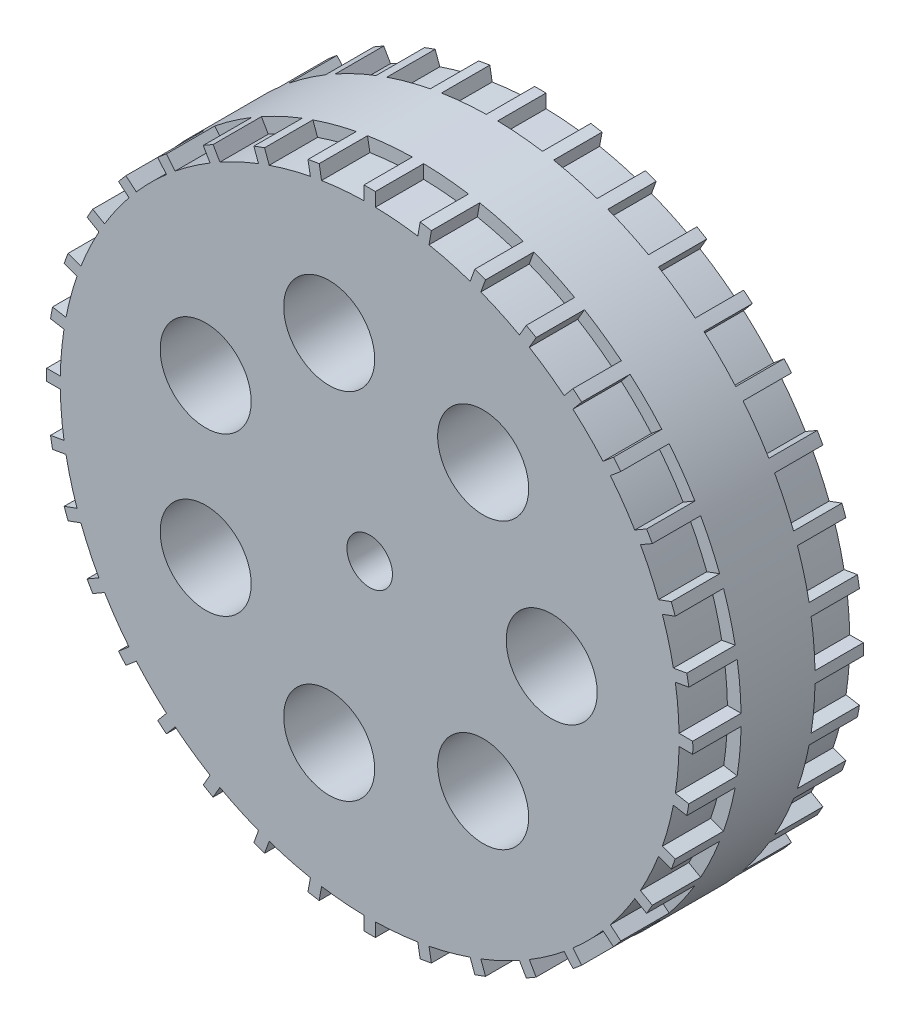
SolidWorks part; units mm, degrees
material "ABS"
ref_plane "前视基准面" through (0, 0, 0) normal (0, 0, 1) x (1, 0, 0)
ref_plane "上视基准面" through (0, 0, 0) normal (0, 1, 0) x (1, 0, 0)
ref_plane "右视基准面" through (0, 0, 0) normal (1, 0, 0) x (0, 0, -1)
sketch "草图1" plane through (0, 0, 0) normal (0, 0, 1) x (1, 0, 0)
  circle A0 centre (0, 0) radius 27.2
  dimension "D1" = 54.4
extrude "凸台-拉伸1" add sketch "草图1" along normal blind 15
sketch "草图2" plane through (0, 0, 0) normal (0, 0, -1) x (-1, 0, 0)
  line L1 (7.0437, 0) -> (3.5218, 6.1)
  line L2 (3.5218, 6.1) -> (-3.5218, 6.1)
  line L3 (-3.5218, 6.1) -> (-7.0437, 0)
  line L4 (-7.0437, 0) -> (-3.5218, -6.1)
  line L5 (-3.5218, -6.1) -> (3.5218, -6.1)
  line L6 (3.5218, -6.1) -> (7.0437, 0)
  circle A0 centre (0, 0) radius 6.1 construction
  dimension "D1" = 12.2
extrude "切除-拉伸1" cut sketch "草图2" against normal blind 10
sketch "草图3" plane through (0, 0, 10) normal (0, 0, -1) x (-1, 0, 0)
  circle A0 centre (0, 0) radius 2
  dimension "D1" = 4
extrude "切除-拉伸2" cut sketch "草图3" against normal blind 11
sketch "草图6" plane through (0, 0, 15) normal (0, 0, 1) x (1, 0, 0)
  circle A0 centre (16, 0) radius 4
  circle A1 centre (9.9758, -12.5093) radius 4
  circle A2 centre (-3.5603, -15.5988) radius 4
  circle A3 centre (-14.4155, -6.9421) radius 4
  circle A4 centre (-14.4155, 6.9421) radius 4
  circle A5 centre (-3.5603, 15.5988) radius 4
  circle A6 centre (9.9758, 12.5093) radius 4
  circle A7 centre (0, 0) radius 2 construction
  point P16 (0, 0)
  point P19 (0, 0)
  dimension "D1" = 8
  dimension "D2" = 7
  dimension "D3" = 16
extrude "切除-拉伸5" cut sketch "草图6" against normal blind 30
sketch "草图7" plane through (0, 0, 15) normal (0, 0, 1) x (1, 0, 0)
  line L0 (0, 27.2) -> (0, 28.4) construction
  line L1 (-0.5, 28.3956) -> (-0.5, 27.1954)
  line L2 (0.5, 28.3956) -> (0.5, 27.1954)
  line L3 (4.4384, 28.051) -> (4.23, 26.8691)
  line L4 (5.4232, 27.8774) -> (5.2148, 26.6954)
  line L5 (9.242, 26.8541) -> (8.8315, 25.7263)
  line L6 (10.1817, 26.5121) -> (9.7712, 25.3843)
  line L7 (13.7648, 24.8413) -> (13.1647, 23.8019)
  line L8 (14.6308, 24.3413) -> (14.0307, 23.3019)
  line L9 (17.8693, 22.0737) -> (17.0978, 21.1543)
  line L10 (18.6354, 21.4309) -> (17.8639, 20.5115)
  line L11 (21.4309, 18.6354) -> (20.5115, 17.8639)
  line L12 (22.0737, 17.8693) -> (21.1543, 17.0978)
  line L13 (24.3413, 14.6308) -> (23.3019, 14.0307)
  line L14 (24.8413, 13.7648) -> (23.8019, 13.1647)
  line L15 (26.5121, 10.1817) -> (25.3843, 9.7712)
  line L16 (26.8541, 9.242) -> (25.7263, 8.8315)
  line L17 (27.8774, 5.4232) -> (26.6954, 5.2148)
  line L18 (28.051, 4.4384) -> (26.8691, 4.23)
  line L19 (28.3956, 0.5) -> (27.1954, 0.5)
  line L20 (28.3956, -0.5) -> (27.1954, -0.5)
  line L21 (28.051, -4.4384) -> (26.8691, -4.23)
  line L22 (27.8774, -5.4232) -> (26.6954, -5.2148)
  line L23 (26.8541, -9.242) -> (25.7263, -8.8315)
  line L24 (26.5121, -10.1817) -> (25.3843, -9.7712)
  line L25 (24.8413, -13.7648) -> (23.8019, -13.1647)
  line L26 (24.3413, -14.6308) -> (23.3019, -14.0307)
  line L27 (22.0737, -17.8693) -> (21.1543, -17.0978)
  line L28 (21.4309, -18.6354) -> (20.5115, -17.8639)
  line L29 (18.6354, -21.4309) -> (17.8639, -20.5115)
  line L30 (17.8693, -22.0737) -> (17.0978, -21.1543)
  line L31 (14.6308, -24.3413) -> (14.0307, -23.3019)
  line L32 (13.7648, -24.8413) -> (13.1647, -23.8019)
  line L33 (10.1817, -26.5121) -> (9.7712, -25.3843)
  line L34 (9.242, -26.8541) -> (8.8315, -25.7263)
  line L35 (5.4232, -27.8774) -> (5.2148, -26.6954)
  line L36 (4.4384, -28.051) -> (4.23, -26.8691)
  line L37 (0.5, -28.3956) -> (0.5, -27.1954)
  line L38 (-0.5, -28.3956) -> (-0.5, -27.1954)
  line L39 (-4.4384, -28.051) -> (-4.23, -26.8691)
  line L40 (-5.4232, -27.8774) -> (-5.2148, -26.6954)
  line L41 (-9.242, -26.8541) -> (-8.8315, -25.7263)
  line L42 (-10.1817, -26.5121) -> (-9.7712, -25.3843)
  line L43 (-13.7648, -24.8413) -> (-13.1647, -23.8019)
  line L44 (-14.6308, -24.3413) -> (-14.0307, -23.3019)
  line L45 (-17.8693, -22.0737) -> (-17.0978, -21.1543)
  line L46 (-18.6354, -21.4309) -> (-17.8639, -20.5115)
  line L47 (-21.4309, -18.6354) -> (-20.5115, -17.8639)
  line L48 (-22.0737, -17.8693) -> (-21.1543, -17.0978)
  line L49 (-24.3413, -14.6308) -> (-23.3019, -14.0307)
  line L50 (-24.8413, -13.7648) -> (-23.8019, -13.1647)
  line L51 (-26.5121, -10.1817) -> (-25.3843, -9.7712)
  line L52 (-26.8541, -9.242) -> (-25.7263, -8.8315)
  line L53 (-27.8774, -5.4232) -> (-26.6954, -5.2148)
  line L54 (-28.051, -4.4384) -> (-26.8691, -4.23)
  line L55 (-28.3956, -0.5) -> (-27.1954, -0.5)
  line L56 (-28.3956, 0.5) -> (-27.1954, 0.5)
  line L57 (-28.051, 4.4384) -> (-26.8691, 4.23)
  line L58 (-27.8774, 5.4232) -> (-26.6954, 5.2148)
  line L59 (-26.8541, 9.242) -> (-25.7263, 8.8315)
  line L60 (-26.5121, 10.1817) -> (-25.3843, 9.7712)
  line L61 (-24.8413, 13.7648) -> (-23.8019, 13.1647)
  line L62 (-24.3413, 14.6308) -> (-23.3019, 14.0307)
  line L63 (-22.0737, 17.8693) -> (-21.1543, 17.0978)
  line L64 (-21.4309, 18.6354) -> (-20.5115, 17.8639)
  line L65 (-18.6354, 21.4309) -> (-17.8639, 20.5115)
  line L66 (-17.8693, 22.0737) -> (-17.0978, 21.1543)
  line L67 (-14.6308, 24.3413) -> (-14.0307, 23.3019)
  line L68 (-13.7648, 24.8413) -> (-13.1647, 23.8019)
  line L69 (-10.1817, 26.5121) -> (-9.7712, 25.3843)
  line L70 (-9.242, 26.8541) -> (-8.8315, 25.7263)
  line L71 (-5.4232, 27.8774) -> (-5.2148, 26.6954)
  line L72 (-4.4384, 28.051) -> (-4.23, 26.8691)
  arc A0 (0.5, 27.1954) -> (-0.5, 27.1954) centre (0, 0) ccw
  arc A1 (0.5, 28.3956) -> (-0.5, 28.3956) centre (0, 0) ccw
  arc A2 (5.4232, 27.8774) -> (4.4384, 28.051) centre (0, 0) ccw
  arc A3 (5.2148, 26.6954) -> (4.23, 26.8691) centre (0, 0) ccw
  arc A4 (10.1817, 26.5121) -> (9.242, 26.8541) centre (0, 0) ccw
  arc A5 (9.7712, 25.3843) -> (8.8315, 25.7263) centre (0, 0) ccw
  arc A6 (14.6308, 24.3413) -> (13.7648, 24.8413) centre (0, 0) ccw
  arc A7 (14.0307, 23.3019) -> (13.1647, 23.8019) centre (0, 0) ccw
  arc A8 (18.6354, 21.4309) -> (17.8693, 22.0737) centre (0, 0) ccw
  arc A9 (17.8639, 20.5115) -> (17.0978, 21.1543) centre (0, 0) ccw
  arc A10 (22.0737, 17.8693) -> (21.4309, 18.6354) centre (0, 0) ccw
  arc A11 (21.1543, 17.0978) -> (20.5115, 17.8639) centre (0, 0) ccw
  arc A12 (24.8413, 13.7648) -> (24.3413, 14.6308) centre (0, 0) ccw
  arc A13 (23.8019, 13.1647) -> (23.3019, 14.0307) centre (0, 0) ccw
  arc A14 (26.8541, 9.242) -> (26.5121, 10.1817) centre (0, 0) ccw
  arc A15 (25.7263, 8.8315) -> (25.3843, 9.7712) centre (0, 0) ccw
  arc A16 (28.051, 4.4384) -> (27.8774, 5.4232) centre (0, 0) ccw
  arc A17 (26.8691, 4.23) -> (26.6954, 5.2148) centre (0, 0) ccw
  arc A18 (28.3956, -0.5) -> (28.3956, 0.5) centre (0, 0) ccw
  arc A19 (27.1954, -0.5) -> (27.1954, 0.5) centre (0, 0) ccw
  arc A20 (27.8774, -5.4232) -> (28.051, -4.4384) centre (0, 0) ccw
  arc A21 (26.6954, -5.2148) -> (26.8691, -4.23) centre (0, 0) ccw
  arc A22 (26.5121, -10.1817) -> (26.8541, -9.242) centre (0, 0) ccw
  arc A23 (25.3843, -9.7712) -> (25.7263, -8.8315) centre (0, 0) ccw
  arc A24 (24.3413, -14.6308) -> (24.8413, -13.7648) centre (0, 0) ccw
  arc A25 (23.3019, -14.0307) -> (23.8019, -13.1647) centre (0, 0) ccw
  arc A26 (21.4309, -18.6354) -> (22.0737, -17.8693) centre (0, 0) ccw
  arc A27 (20.5115, -17.8639) -> (21.1543, -17.0978) centre (0, 0) ccw
  arc A28 (17.8693, -22.0737) -> (18.6354, -21.4309) centre (0, 0) ccw
  arc A29 (17.0978, -21.1543) -> (17.8639, -20.5115) centre (0, 0) ccw
  arc A30 (13.7648, -24.8413) -> (14.6308, -24.3413) centre (0, 0) ccw
  arc A31 (13.1647, -23.8019) -> (14.0307, -23.3019) centre (0, 0) ccw
  arc A32 (9.242, -26.8541) -> (10.1817, -26.5121) centre (0, 0) ccw
  arc A33 (8.8315, -25.7263) -> (9.7712, -25.3843) centre (0, 0) ccw
  arc A34 (4.4384, -28.051) -> (5.4232, -27.8774) centre (0, 0) ccw
  arc A35 (4.23, -26.8691) -> (5.2148, -26.6954) centre (0, 0) ccw
  arc A36 (-0.5, -28.3956) -> (0.5, -28.3956) centre (0, 0) ccw
  arc A37 (-0.5, -27.1954) -> (0.5, -27.1954) centre (0, 0) ccw
  arc A38 (-5.4232, -27.8774) -> (-4.4384, -28.051) centre (0, 0) ccw
  arc A39 (-5.2148, -26.6954) -> (-4.23, -26.8691) centre (0, 0) ccw
  arc A40 (-10.1817, -26.5121) -> (-9.242, -26.8541) centre (0, 0) ccw
  arc A41 (-9.7712, -25.3843) -> (-8.8315, -25.7263) centre (0, 0) ccw
  arc A42 (-14.6308, -24.3413) -> (-13.7648, -24.8413) centre (0, 0) ccw
  arc A43 (-14.0307, -23.3019) -> (-13.1647, -23.8019) centre (0, 0) ccw
  arc A44 (-18.6354, -21.4309) -> (-17.8693, -22.0737) centre (0, 0) ccw
  arc A45 (-17.8639, -20.5115) -> (-17.0978, -21.1543) centre (0, 0) ccw
  arc A46 (-22.0737, -17.8693) -> (-21.4309, -18.6354) centre (0, 0) ccw
  arc A47 (-21.1543, -17.0978) -> (-20.5115, -17.8639) centre (0, 0) ccw
  arc A48 (-24.8413, -13.7648) -> (-24.3413, -14.6308) centre (0, 0) ccw
  arc A49 (-23.8019, -13.1647) -> (-23.3019, -14.0307) centre (0, 0) ccw
  arc A50 (-26.8541, -9.242) -> (-26.5121, -10.1817) centre (0, 0) ccw
  arc A51 (-25.7263, -8.8315) -> (-25.3843, -9.7712) centre (0, 0) ccw
  arc A52 (-28.051, -4.4384) -> (-27.8774, -5.4232) centre (0, 0) ccw
  arc A53 (-26.8691, -4.23) -> (-26.6954, -5.2148) centre (0, 0) ccw
  arc A54 (-28.3956, 0.5) -> (-28.3956, -0.5) centre (0, 0) ccw
  arc A55 (-27.1954, 0.5) -> (-27.1954, -0.5) centre (0, 0) ccw
  arc A56 (-27.8774, 5.4232) -> (-28.051, 4.4384) centre (0, 0) ccw
  arc A57 (-26.6954, 5.2148) -> (-26.8691, 4.23) centre (0, 0) ccw
  arc A58 (-26.5121, 10.1817) -> (-26.8541, 9.242) centre (0, 0) ccw
  arc A59 (-25.3843, 9.7712) -> (-25.7263, 8.8315) centre (0, 0) ccw
  arc A60 (-24.3413, 14.6308) -> (-24.8413, 13.7648) centre (0, 0) ccw
  arc A61 (-23.3019, 14.0307) -> (-23.8019, 13.1647) centre (0, 0) ccw
  arc A62 (-21.4309, 18.6354) -> (-22.0737, 17.8693) centre (0, 0) ccw
  arc A63 (-20.5115, 17.8639) -> (-21.1543, 17.0978) centre (0, 0) ccw
  arc A64 (-17.8693, 22.0737) -> (-18.6354, 21.4309) centre (0, 0) ccw
  arc A65 (-17.0978, 21.1543) -> (-17.8639, 20.5115) centre (0, 0) ccw
  arc A66 (-13.7648, 24.8413) -> (-14.6308, 24.3413) centre (0, 0) ccw
  arc A67 (-13.1647, 23.8019) -> (-14.0307, 23.3019) centre (0, 0) ccw
  arc A68 (-9.242, 26.8541) -> (-10.1817, 26.5121) centre (0, 0) ccw
  arc A69 (-8.8315, 25.7263) -> (-9.7712, 25.3843) centre (0, 0) ccw
  arc A70 (-4.4384, 28.051) -> (-5.4232, 27.8774) centre (0, 0) ccw
  arc A71 (-4.23, 26.8691) -> (-5.2148, 26.6954) centre (0, 0) ccw
  point P150 (0, 0)
  dimension "D1" = 54.4
  dimension "D2" = 56.8
  dimension "D3" = 0.5
  dimension "D4" = 36
extrude "凸台-拉伸2" add sketch "草图7" against normal up to surface (15 mm away) up to face at (13.9758, -12.5093, 0)
ref_plane "基准面1" through (0, 0, 7.5) normal (0, 0, 1) x (1, 0, 0)
sketch "草图10" plane through (0, 0, 7.5) normal (0, 0, 1) x (1, 0, 0)
  circle A0 centre (0, 0) radius 28.4
  circle A1 centre (0, 0) radius 27.2
extrude "凸台-拉伸3" add sketch "草图10" along normal blind 3.25
mirror "镜向1" about plane through (0, 0, 7.5) normal (0, 0, 1) of "凸台-拉伸3"
